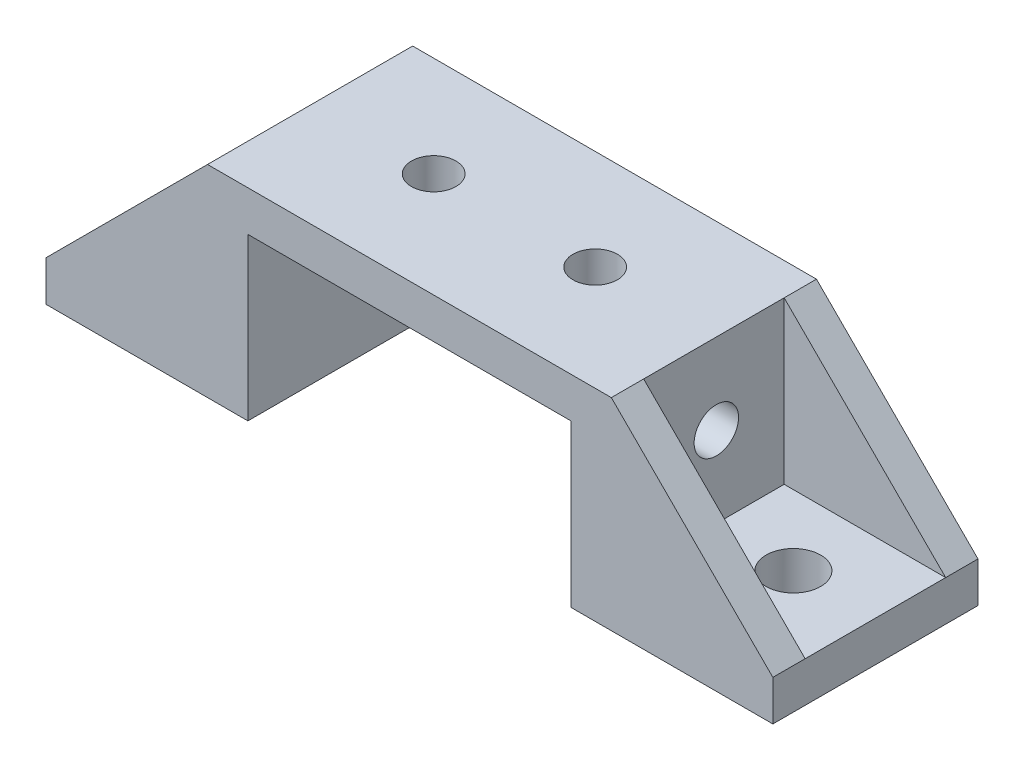
SolidWorks part; units mm, degrees
ref_plane "Front Plane" through (0, 0, 0) normal (0, 0, 1) x (1, 0, 0)
ref_plane "Top Plane" through (0, 0, 0) normal (0, 1, 0) x (1, 0, 0)
ref_plane "Right Plane" through (0, 0, 0) normal (1, 0, 0) x (0, 0, -1)
sketch "Sketch1" plane through (0, 0, 0) normal (0, 0, 1) x (1, 0, 0)
  line L0 (-25, 15) -> (-45, -5)
  line L1 (-20, -10) -> (20, -10)
  line L2 (-20, -10) -> (-20, 10)
  line L3 (-20, 10) -> (20, 10)
  line L4 (20, -10) -> (20, 10)
  line L5 (-20, -10) -> (20, 10) construction
  line L6 (-20, 10) -> (20, -10) construction
  line L7 (-20, -10) -> (-25, -10)
  line L8 (-20, -10) -> (-20, 15)
  line L9 (-20, 15) -> (-25, 15)
  line L10 (-25, -10) -> (-25, 15)
  line L11 (-20, 15) -> (0, 15)
  line L12 (-20, 15) -> (-20, 10)
  line L13 (-20, 10) -> (0, 10)
  line L14 (0, 15) -> (0, 10)
  line L16 (-45, -5) -> (-25, -5)
  line L17 (-45, -5) -> (-45, -10)
  line L18 (-45, -10) -> (-25, -10)
  line L19 (-25, -5) -> (-25, -10)
  point P0 (0, 0)
  dimension "D1" = 40
  dimension "D2" = 20
  dimension "D3" = 45
  dimension "D4" = 5
extrude "Boss-Extrude1" add sketch "Sketch1" along normal blind 25.4 contours L14 L11 L8 L3 | L10 L7 L2 L8 L9 | L17 L18 L10 L16 region at (-22.5, 2.5, 0) region at (-35, -7.5, 0) region at (-10, 12.5, 0)
extrude "Boss-Extrude2" add sketch "Sketch1<3>" along normal blind 4 contours L0 L16 L10 region at (-31.6667, 1.6667, 0)
sketch "Sketch1<3>" plane through (0, 0, 0) normal (0, 0, 1) x (1, 0, 0) same geometry as "Sketch1"
ref_plane "Plane1" through (0, 0, 12.7) normal (0, 0, 1) x (1, 0, 0)
mirror "Mirror1" about plane through (0, 0, 12.7) normal (0, 0, 1) of "Boss-Extrude2"
hole_wizard "M5 Clearance Hole1" positions "Sketch2" profile "Sketch3" hole size "M5" standard "ANSI Metric"
sketch "Sketch2" plane through (0, 15, 0) normal (0, 1, 0) x (1, 0, 0)
  line L0 (-25, -25.4) -> (0, -25.4) construction
  line L1 (0, -25.4) -> (0, 0) construction
  point P0 (-10, -12.4)
  dimension "D1" = 13
  dimension "D2" = 10
sketch "Sketch3" plane through (-10, 15, 12.4) normal (1, 0, 0) x (0, 0, 1)
  line L0 (0, 0) -> (0, 13.6524)
  line L1 (0, 13.6524) -> (2.75, 12)
  line L2 (2.75, 12) -> (2.75, 0)
  line L5 (2.75, 0) -> (0, 0)
  line L10 (0, 13.6524) -> (-2.75, 12) construction
  line L11 (0, -6.35) -> (0, 107.95) construction
  dimension "Hole Dia." = 5.5
  dimension "Hole Depth" = 12
  dimension "Drill Angle" = 118
hole_wizard "M5 Clearance Hole2" positions "Sketch4" profile "Sketch5" hole size "M5" standard "ANSI Metric"
sketch "Sketch4" plane through (-25, 0, 0) normal (-1, 0, 0) x (0, 0, 1)
  line L0 (21.4, 15) -> (4, 15) construction
  point P0 (12.4, 5)
  dimension "D1" = 10
  dimension "D2" = 13
sketch "Sketch5" plane through (-25, 5, 12.4) normal (0, 1, 0) x (0, 0, 1)
  line L0 (0, 0) -> (0, 13.6524)
  line L1 (0, 13.6524) -> (2.75, 12)
  line L2 (2.75, 12) -> (2.75, 0)
  line L5 (2.75, 0) -> (0, 0)
  line L10 (0, 13.6524) -> (-2.75, 12) construction
  line L11 (0, -6.35) -> (0, 107.95) construction
  dimension "Hole Dia." = 5.5
  dimension "Hole Depth" = 12
  dimension "Drill Angle" = 118
hole_wizard "1/4 Clearance Hole1" positions "Sketch6" profile "Sketch7" hole size "1/4" standard "ANSI Inch"
sketch "Sketch6" plane through (0, -5, 0) normal (0, 1, 0) x (1, 0, 0)
  line L0 (-45, -21.4) -> (-45, -4) construction
  point P0 (-34.84, -12.7)
  dimension "D1" = 12.7
  dimension "D2" = 10.16
sketch "Sketch7" plane through (-34.84, -5, 12.7) normal (1, 0, 0) x (0, 0, 1)
  line L0 (0, 0) -> (0, 14.0298)
  line L1 (0, 14.0298) -> (3.3782, 12)
  line L2 (3.3782, 12) -> (3.3782, 0)
  line L5 (3.3782, 0) -> (0, 0)
  line L10 (0, 14.0298) -> (-3.3782, 12) construction
  line L11 (0, -6.35) -> (0, 107.95) construction
  dimension "Hole Dia." = 6.7564
  dimension "Hole Depth" = 12
  dimension "Drill Angle" = 118
mirror "Mirror2" about plane through (0, 0, 0) normal (1, 0, 0) of "Mirror1", "1/4 Clearance Hole1", "M5 Clearance Hole2", "M5 Clearance Hole1", "Boss-Extrude2", "Boss-Extrude1"
